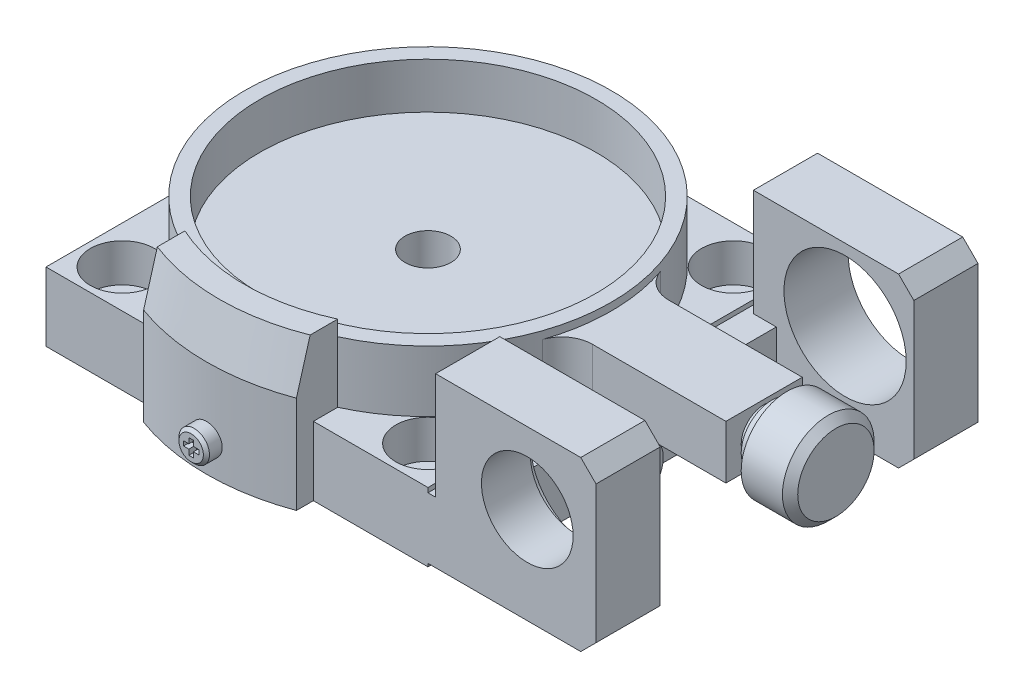
SolidWorks part; units mm, degrees
ref_plane "前视基准面" through (0, 0, 0) normal (0, 0, 1) x (1, 0, 0)
ref_plane "上视基准面" through (0, 0, 0) normal (0, 1, 0) x (1, 0, 0)
ref_plane "右视基准面" through (0, 0, 0) normal (1, 0, 0) x (0, 0, -1)
sketch "草图1" plane through (0, 0, 0) normal (0, 0, 1) x (1, 0, 0)
  line L0 (-12.5, 0) -> (12.5, 0)
  line L1 (12.5, 0) -> (12.5, 4.5)
  line L2 (12.5, 4.5) -> (-12.5, 4.5)
  line L3 (-12.5, 4.5) -> (-12.5, 0)
extrude "凸台-拉伸1" add sketch "草图1" against normal blind 12.5 and the other way blind 12.5
sketch "草图2" plane through (0, 0, 0) normal (1, 0, 0) x (0, 0, -1)
  line L0 (0, 4.5) -> (-12, 4.5)
  line L1 (-12, 4.5) -> (-12, 8.5)
  line L2 (-12, 8.5) -> (-11, 8.5)
  line L3 (-11, 8.5) -> (-11, 5.5)
  line L4 (-11, 5.5) -> (0, 5.5)
  line L5 (0, 5.5) -> (0, 4.5)
  line L6 (0, 5.5) -> (0, 4.5) construction
revolve "旋转1" add sketch "草图2" angle 360 about L6
sketch "草图3" plane through (0, 0, 0) normal (0, 1, 0) x (1, 0, 0)
  line L0 (-12.5, 4.5) -> (-12.5, -4.5)
  line L1 (-12.5, -4.5) -> (-4.5, -4.5)
  line L2 (-4.5, -4.5) -> (-4.5, -12.5)
  line L3 (-4.5, -12.5) -> (4.5, -12.5)
  line L4 (4.5, -12.5) -> (4.5, -4.5)
  line L5 (4.5, -4.5) -> (12.5, -4.5)
  line L6 (12.5, -4.5) -> (12.5, 4.5)
  line L7 (12.5, 4.5) -> (4.5, 4.5)
  line L8 (4.5, 4.5) -> (4.5, 12.5)
  line L9 (4.5, 12.5) -> (-4.5, 12.5)
  line L10 (-4.5, 12.5) -> (-4.5, 4.5)
  line L11 (-4.5, 4.5) -> (-12.5, 4.5)
extrude "切除-拉伸1" cut sketch "草图3" along normal blind 0.2 and the other way blind 0.2
ref_plane "基准面4" through (-10, 0, 0) normal (1, 0, 0) x (0, 0, -1)
sketch "草图4" plane through (-10, 0, 0) normal (1, 0, 0) x (0, 0, -1)
  line L0 (10, 0) -> (8.75, 0)
  line L1 (8.75, 0) -> (8.75, 2)
  line L2 (8.75, 2) -> (7.9, 2)
  line L3 (7.9, 2) -> (7.9, 4.5)
  line L4 (7.9, 4.5) -> (10, 4.5)
  line L5 (10, 4.5) -> (10, 0)
  line L6 (10, 4.5) -> (10, 0) construction
revolve "切除-旋转1" cut sketch "草图4" angle 360 about L6
sketch "草图5" plane through (0, 0, 0) normal (0, 1, 0) x (1, 0, 0)
  line L0 (-10, 10) -> (990, 10)
  line L1 (-10, 10) -> (-10, -990)
pattern_linear "阵列(线性)1" count 2 spacing 20 along (1, 0, 0) count 2 spacing 20 along (0, 0, 1) of "切除-旋转1"
ref_plane "基准面5" through (0, 4.5, 0) normal (0, 1, 0) x (1, 0, 0)
sketch "草图6" plane through (0, 4.5, 0) normal (0, 1, 0) x (1, 0, 0)
  line L0 (11.3632, 3.8571) -> (11.3632, -3.8571)
  line L1 (13.2571, -2.5) -> (22, -2.5)
  line L2 (22, -2.5) -> (22, 2.5)
  line L3 (22, 2.5) -> (13.2571, 2.5)
  arc A0 (11.3632, -3.8571) -> (13.2571, -2.5) centre (13.2571, -4.5) cw
  arc A1 (13.2571, 2.5) -> (11.3632, 3.8571) centre (13.2571, 4.5) cw
extrude "凸台-拉伸2" add sketch "草图6" along normal blind 3.5
sketch "草图7" plane through (0, 0, 0) normal (0, 0, 1) x (1, 0, 0)
  line L0 (21.9, 6.2) -> (21.9, 7.7)
  line L1 (21.9, 7.7) -> (22.5, 7.7)
  line L2 (22.5, 7.7) -> (22.5, 8.2)
  line L3 (22.5, 8.2) -> (23.5, 8.2)
  line L4 (23.5, 8.2) -> (23.5, 9.2)
  line L5 (23.5, 9.2) -> (26.2, 9.2)
  line L6 (26.2, 9.2) -> (26.7, 8.7)
  line L7 (26.7, 8.7) -> (26.7, 6.2)
  line L8 (26.7, 6.2) -> (21.9, 6.2)
  line L9 (26.7, 6.2) -> (21.9, 6.2) construction
revolve "旋转2" add sketch "草图7" angle 360 about L9 reverse direction yes
ref_plane "基准面6" through (12.5, 0, 0) normal (1, 0, 0) x (0, 0, -1)
sketch "草图8" plane through (12.5, 0, 0) normal (1, 0, 0) x (0, 0, -1)
  line L0 (-12.5, 0.2) -> (12.5, 0.2)
  line L1 (12.5, 0.2) -> (12.5, 4.2)
  line L2 (12.5, 4.2) -> (-12.5, 4.2)
  line L3 (-12.5, 4.2) -> (-12.5, 0.2)
extrude "凸台-拉伸3" add sketch "草图8" along normal blind 2
ref_plane "基准面7" through (-12.5, 0, 0) normal (1, 0, 0) x (0, 0, -1)
ref_plane "基准面8" through (0, 0, 12.5) normal (0, 0, 1) x (1, 0, 0)
sketch "草图9" plane through (0, 0, 12.5) normal (0, 0, 1) x (1, 0, 0)
  line L0 (13, 0.2) -> (22.5, 0.2)
  line L1 (22.5, 0.2) -> (23.5, 1.2)
  line L2 (23.5, 1.2) -> (23.5, 10.2)
  line L3 (23.5, 10.2) -> (22.5, 11.2)
  line L4 (22.5, 11.2) -> (13, 11.2)
  line L5 (13, 11.2) -> (13, 0.2)
extrude "凸台-拉伸4" add sketch "草图9" against normal blind 4.2
sketch "草图10" plane through (0, 0, 12.5) normal (0, 0, 1) x (1, 0, 0)
  circle A0 centre (19, 6.5) radius 3
extrude "切除-拉伸2" cut sketch "草图10" against normal blind 4.2
ref_plane "基准面9" through (0, 0, -12.5) normal (0, 0, 1) x (1, 0, 0)
sketch "草图11" plane through (0, 0, -12.5) normal (0, 0, 1) x (1, 0, 0)
  line L0 (13, 0.2) -> (22.5, 0.2)
  line L1 (22.5, 0.2) -> (23.5, 1.2)
  line L2 (23.5, 1.2) -> (23.5, 10.2)
  line L3 (23.5, 10.2) -> (22.5, 11.2)
  line L4 (22.5, 11.2) -> (13, 11.2)
  line L5 (13, 11.2) -> (13, 0.2)
extrude "凸台-拉伸5" add sketch "草图11" along normal blind 4.2
sketch "草图12" plane through (0, 0, -12.5) normal (0, 0, 1) x (1, 0, 0)
  circle A0 centre (19, 6.5) radius 4
extrude "切除-拉伸3" cut sketch "草图12" along normal blind 4.2
ref_plane "基准面10" through (0, 0, -3) normal (0, 0, 1) x (1, 0, 0)
sketch "草图13" plane through (0, 0, -3) normal (0, 0, 1) x (1, 0, 0)
  line L0 (14.5, 2.5) -> (14.5, 4.4)
  line L1 (14.5, 4.4) -> (16.5, 4.4)
  line L2 (16.5, 4.4) -> (16.5, 2.5)
  line L3 (16.5, 2.5) -> (14.5, 2.5)
  line L4 (16.5, 2.5) -> (14.5, 2.5) construction
revolve "旋转3" add sketch "草图13" angle 360 about L4 reverse direction yes
ref_plane "基准面11" through (16.5, 0, 0) normal (1, 0, 0) x (0, 0, -1)
sketch "草图14" plane through (16.5, 0, 0) normal (1, 0, 0) x (0, 0, -1)
  line L0 (2.567, 1.75) -> (3.433, 1.75)
  line L1 (3.433, 1.75) -> (3.866, 2.5)
  line L2 (3.866, 2.5) -> (3.433, 3.25)
  line L3 (3.433, 3.25) -> (2.567, 3.25)
  line L4 (2.567, 3.25) -> (2.134, 2.5)
  line L5 (2.134, 2.5) -> (2.567, 1.75)
extrude "切除-拉伸4" cut sketch "草图14" against normal blind 1
ref_plane "基准面12" through (0, 0, 8.3) normal (0, 0, 1) x (1, 0, 0)
sketch "草图15" plane through (0, 0, 8.3) normal (0, 0, 1) x (1, 0, 0)
  circle A0 centre (19, 6.2) radius 4
extrude "切除-拉伸5" cut sketch "草图15" along normal blind 1
ref_plane "基准面13" through (0, 0, 3) normal (0, 0, 1) x (1, 0, 0)
sketch "草图16" plane through (0, 0, 3) normal (0, 0, 1) x (1, 0, 0)
  line L0 (14.5, 2.5) -> (14.5, 4.4)
  line L1 (14.5, 4.4) -> (16.5, 4.4)
  line L2 (16.5, 4.4) -> (16.5, 2.5)
  line L3 (16.5, 2.5) -> (14.5, 2.5)
  line L4 (16.5, 2.5) -> (14.5, 2.5) construction
revolve "旋转4" add sketch "草图16" angle 360 about L4 reverse direction yes
ref_plane "基准面14" through (16.5, 0, 0) normal (1, 0, 0) x (0, 0, -1)
sketch "草图17" plane through (16.5, 0, 0) normal (1, 0, 0) x (0, 0, -1)
  line L0 (-3.433, 1.75) -> (-2.567, 1.75)
  line L1 (-2.567, 1.75) -> (-2.134, 2.5)
  line L2 (-2.134, 2.5) -> (-2.567, 3.25)
  line L3 (-2.567, 3.25) -> (-3.433, 3.25)
  line L4 (-3.433, 3.25) -> (-3.866, 2.5)
  line L5 (-3.866, 2.5) -> (-3.433, 1.75)
extrude "切除-拉伸6" cut sketch "草图17" against normal blind 1
ref_plane "基准面15" through (0, 8.5, 0) normal (0, 1, 0) x (1, 0, 0)
ref_plane "基准面16" through (0, 0, -2.5) normal (0, 0, 1) x (1, 0, 0)
ref_plane "基准面17" through (0, 0, 2.5) normal (0, 0, 1) x (1, 0, 0)
ref_plane "基准面18" through (0, 0, 0) normal (0, 1, 0) x (1, 0, 0)
sketch "草图18" plane through (0, 0, 0) normal (0, 1, 0) x (1, 0, 0)
  line L0 (5, -13.6107) -> (5, -10.9087)
  line L1 (-5, -10.9087) -> (-5, -13.6107)
  arc A0 (-5, -13.6107) -> (5, -13.6107) centre (0, 0) ccw
  arc A1 (5, -10.9087) -> (-5, -10.9087) centre (0, 0) cw
extrude "凸台-拉伸6" add sketch "草图18" along normal blind 9.5
sketch "草图19" plane through (0, 0, 0) normal (1, 0, 0) x (0, 0, -1)
  line L0 (-16, 4.5) -> (-15, 4.5)
  line L1 (-15, 4.5) -> (-13.6067, 9.7)
  line L2 (-13.6067, 9.7) -> (-16, 9.7)
  line L3 (-16, 9.7) -> (-16, 4.5)
  line L4 (0, 9.7) -> (0, 4.5) construction
revolve "切除-旋转2" cut sketch "草图19" angle 50 about L4 other way angle 50 reverse direction yes
sketch "草图20" plane through (0, 0, 0) normal (1, 0, 0) x (0, 0, -1)
  line L0 (-14, 2) -> (-14, 1)
  line L1 (-14, 1) -> (-15.3, 1)
  line L2 (-15.3, 1) -> (-15.5, 1.2)
  line L3 (-15.5, 1.2) -> (-15.5, 2)
  line L4 (-15.5, 2) -> (-14, 2)
  line L5 (-15.5, 2) -> (-14, 2) construction
revolve "旋转5" add sketch "草图20" angle 360 about L5
ref_plane "基准面19" through (0, 0, 15.5) normal (0, 0, 1) x (1, 0, 0)
sketch "草图21" plane through (0, 0, 15.5) normal (0, 0, 1) x (1, 0, 0)
  line L0 (0.15, 2.5) -> (-0.15, 2.5)
  line L1 (-0.15, 2.5) -> (-0.15, 2.15)
  line L2 (-0.15, 2.15) -> (-0.5, 2.15)
  line L3 (-0.5, 2.15) -> (-0.5, 1.85)
  line L4 (-0.5, 1.85) -> (-0.15, 1.85)
  line L5 (-0.15, 1.85) -> (-0.15, 1.5)
  line L6 (-0.15, 1.5) -> (0.15, 1.5)
  line L7 (0.15, 1.5) -> (0.15, 1.85)
  line L8 (0.15, 1.85) -> (0.5, 1.85)
  line L9 (0.5, 1.85) -> (0.5, 2.15)
  line L10 (0.5, 2.15) -> (0.15, 2.15)
  line L11 (0.15, 2.15) -> (0.15, 2.5)
extrude "切除-拉伸7" cut sketch "草图21" against normal blind 0.5
ref_plane "基准面20" through (0, 2, 0) normal (0, 1, 0) x (1, 0, 0)
sketch "草图22" plane through (0, 0, 0) normal (0, 1, 0) x (1, 0, 0)
  circle A0 centre (0, 0) radius 1.5
extrude "切除-拉伸8" cut sketch "草图22" along normal blind 8.5
ref_plane "base XY" through (0, 8.5, 0) normal (0, 1, 0) x (1, 0, 0)
ref_plane "base XZ" through (0, 0, 0) normal (0, 0, 1) x (1, 0, 0)
ref_plane "base YZ" through (0, 0, 0) normal (1, 0, 0) x (0, 0, -1)
ref_axis "base X" through (-80.9, 8.5, 0) along (1, 0, 0)
ref_axis "base Y" through (0, 8.5, 50) along (0, 0, -1)
ref_axis "base Z" through (0, 50, 0) along (0, -1, 0)
sketch3d "base"
  point P0 (0, 8.5, 0)
ref_plane "s_alt1 XY" through (0, 0, -2.5) normal (0, 0, 1) x (1, 0, 0)
ref_plane "s_alt1 XZ" through (0, 6.5, 0) normal (0, -1, 0) x (-1, 0, 0)
ref_plane "s_alt1 YZ" through (-19, 0, 0) normal (1, 0, 0) x (0, 0, -1)
ref_axis "s_alt1 X" through (-80.9, 6.5, -2.5) along (1, 0, 0)
ref_axis "s_alt1 Y" through (-19, -50, -2.5) along (0, 1, 0)
ref_axis "s_alt1 Z" through (-19, 6.5, 80.9) along (0, 0, -1)
sketch3d "s_alt1"
  point P0 (-19, 6.5, -2.5)
ref_plane "s_to_base  XY" through (0, 0, -2.5) normal (0, 0, 1) x (1, 0, 0)
ref_plane "s_to_base  XZ" through (0, 6.5, 0) normal (0, -1, 0) x (-1, 0, 0)
ref_plane "s_to_base  YZ" through (19, 0, 0) normal (1, 0, 0) x (0, 0, -1)
ref_axis "s_to_base  X" through (-80.9, 6.5, -2.5) along (1, 0, 0)
ref_axis "s_to_base  Y" through (19, -50, -2.5) along (0, 1, 0)
ref_axis "s_to_base  Z" through (19, 6.5, 80.9) along (0, 0, -1)
sketch3d "s_to_base "
  point P0 (19, 6.5, -2.5)
ref_plane "fs_to_base XY" through (0, 0, 2.5) normal (0, 0, 1) x (1, 0, 0)
ref_plane "fs_to_base XZ" through (0, 6.5, 0) normal (0, -1, 0) x (-1, 0, 0)
ref_plane "fs_to_base YZ" through (19, 0, 0) normal (1, 0, 0) x (0, 0, -1)
ref_axis "fs_to_base X" through (-80.9, 6.5, 2.5) along (1, 0, 0)
ref_axis "fs_to_base Y" through (19, -50, 2.5) along (0, 1, 0)
ref_axis "fs_to_base Z" through (19, 6.5, 80.9) along (0, 0, -1)
sketch3d "fs_to_base"
  point P0 (19, 6.5, 2.5)
ref_plane "fs_alt1  XY" through (0, 0, 2.5) normal (0, 0, 1) x (1, 0, 0)
ref_plane "fs_alt1  XZ" through (0, 6.5, 0) normal (0, -1, 0) x (-1, 0, 0)
ref_plane "fs_alt1  YZ" through (-19, 0, 0) normal (1, 0, 0) x (0, 0, -1)
ref_axis "fs_alt1  X" through (-80.9, 6.5, 2.5) along (1, 0, 0)
ref_axis "fs_alt1  Y" through (-19, -50, 2.5) along (0, 1, 0)
ref_axis "fs_alt1  Z" through (-19, 6.5, 80.9) along (0, 0, -1)
sketch3d "fs_alt1 "
  point P0 (-19, 6.5, 2.5)
ref_plane "to_lower XY" through (0, 0, 0) normal (0, 1, 0) x (1, 0, 0)
ref_plane "to_lower XZ" through (0, 0, 0) normal (0, 0, 1) x (1, 0, 0)
ref_plane "to_lower YZ" through (0, 0, 0) normal (1, 0, 0) x (0, 0, -1)
ref_axis "to_lower X" through (-80.9, 0, 0) along (1, 0, 0)
ref_axis "to_lower Y" through (0, 0, 50) along (0, 0, -1)
ref_axis "to_lower Z" through (0, 50, 0) along (0, -1, 0)
sketch3d "to_lower"
  point P0 (0, 0, 0)
ref_plane "to_scb 1 XY" through (0, 2, 0) normal (0, 1, 0) x (1, 0, 0)
ref_plane "to_scb 1 XZ" through (0, 0, -10) normal (0, 0, 1) x (1, 0, 0)
ref_plane "to_scb 1 YZ" through (-10, 0, 0) normal (1, 0, 0) x (0, 0, -1)
ref_axis "to_scb 1 X" through (-80.9, 2, -10) along (1, 0, 0)
ref_axis "to_scb 1 Y" through (-10, 2, 50) along (0, 0, -1)
ref_axis "to_scb 1 Z" through (-10, 50, -10) along (0, -1, 0)
sketch3d "to_scb 1"
  point P0 (-10, 2, -10)
ref_plane "to_scb 2 XY" through (0, 2, 0) normal (0, 1, 0) x (1, 0, 0)
ref_plane "to_scb 2 XZ" through (0, 0, -10) normal (0, 0, 1) x (1, 0, 0)
ref_plane "to_scb 2 YZ" through (10, 0, 0) normal (1, 0, 0) x (0, 0, -1)
ref_axis "to_scb 2 X" through (-80.9, 2, -10) along (1, 0, 0)
ref_axis "to_scb 2 Y" through (10, 2, 50) along (0, 0, -1)
ref_axis "to_scb 2 Z" through (10, 50, -10) along (0, -1, 0)
sketch3d "to_scb 2"
  point P0 (10, 2, -10)
ref_plane "to_scb 3 XY" through (0, 2, 0) normal (0, 1, 0) x (1, 0, 0)
ref_plane "to_scb 3 XZ" through (0, 0, 10) normal (0, 0, 1) x (1, 0, 0)
ref_plane "to_scb 3 YZ" through (-10, 0, 0) normal (1, 0, 0) x (0, 0, -1)
ref_axis "to_scb 3 X" through (-80.9, 2, 10) along (1, 0, 0)
ref_axis "to_scb 3 Y" through (-10, 2, 50) along (0, 0, -1)
ref_axis "to_scb 3 Z" through (-10, 50, 10) along (0, -1, 0)
sketch3d "to_scb 3"
  point P0 (-10, 2, 10)
ref_plane "to_scb 4 XY" through (0, 2, 0) normal (0, 1, 0) x (1, 0, 0)
ref_plane "to_scb 4 XZ" through (0, 0, 10) normal (0, 0, 1) x (1, 0, 0)
ref_plane "to_scb 4 YZ" through (10, 0, 0) normal (1, 0, 0) x (0, 0, -1)
ref_axis "to_scb 4 X" through (-80.9, 2, 10) along (1, 0, 0)
ref_axis "to_scb 4 Y" through (10, 2, 50) along (0, 0, -1)
ref_axis "to_scb 4 Z" through (10, 50, 10) along (0, -1, 0)
sketch3d "to_scb 4"
  point P0 (10, 2, 10)
